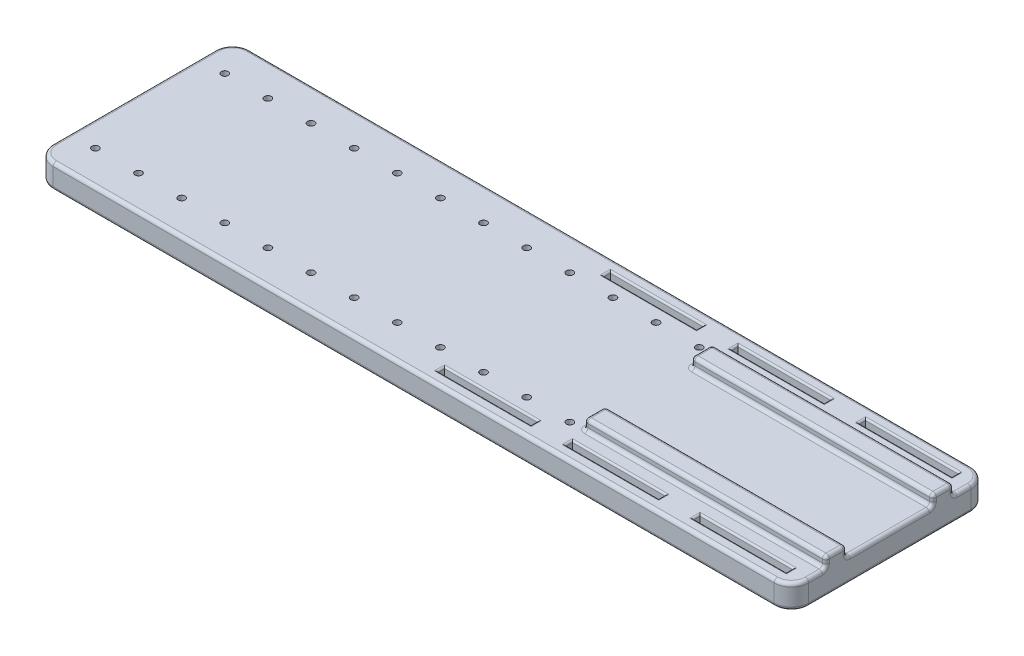
SolidWorks part; units mm, degrees
ref_plane "Front" through (0, 0, 0) normal (0, 0, 1) x (1, 0, 0)
ref_plane "Top" through (0, 0, 0) normal (0, 1, 0) x (1, 0, 0)
ref_plane "Right" through (0, 0, 0) normal (1, 0, 0) x (0, 0, -1)
sketch "Sketch6" plane through (0, 0, 0) normal (0, 0, 1) x (1, 0, 0)
  line L1 (-109.5, 3.5) -> (109.5, 3.5)
  line L2 (-109.5, 3.5) -> (-109.5, -3.5)
  line L3 (-109.5, -3.5) -> (109.5, -3.5)
  line L4 (109.5, 3.5) -> (109.5, -3.5)
  line L5 (-109.5, 3.5) -> (109.5, -3.5) construction
  line L6 (-109.5, -3.5) -> (109.5, 3.5) construction
  point P0 (0, 0)
  dimension "D1" = 219
  dimension "D2" = 7
extrude "Boss-Extrude2" add sketch "Sketch6" along normal mid plane 57
sketch "Sketch2" plane through (0, 3.5, 24.5) normal (0, -1, 0) x (1, 0, 0)
  line L0 (-109.5, -0.5) -> (109.5, -0.5) construction
  line L1 (54, -48.5) -> (54, -0.5) construction
  line L2 (91, -48.5) -> (91, -0.5) construction
  line L3 (17, -0.5) -> (17, -48.5) construction
  line L4 (3.5, 0.5) -> (30.5, 0.5)
  line L5 (3.5, 0.5) -> (3.5, -1.5)
  line L6 (3.5, -1.5) -> (30.5, -1.5)
  line L7 (30.5, 0.5) -> (30.5, -1.5)
  line L8 (3.5, 0.5) -> (30.5, -1.5) construction
  line L9 (3.5, -1.5) -> (30.5, 0.5) construction
  line L10 (40.5, 0.5) -> (67.5, 0.5)
  line L11 (40.5, 0.5) -> (40.5, -1.5)
  line L12 (40.5, -1.5) -> (67.5, -1.5)
  line L13 (67.5, 0.5) -> (67.5, -1.5)
  line L14 (40.5, 0.5) -> (67.5, -1.5) construction
  line L15 (40.5, -1.5) -> (67.5, 0.5) construction
  line L16 (77.5, 0.5) -> (104.5, 0.5)
  line L17 (77.5, 0.5) -> (77.5, -1.5)
  line L18 (77.5, -1.5) -> (104.5, -1.5)
  line L19 (104.5, 0.5) -> (104.5, -1.5)
  line L20 (77.5, 0.5) -> (104.5, -1.5) construction
  line L21 (77.5, -1.5) -> (104.5, 0.5) construction
  line L24 (-109.5, 4) -> (-109.5, -53) construction
  line L25 (109.5, 4) -> (109.5, -53) construction
  line L26 (109.5, 4) -> (-109.5, 4) construction
  line L27 (-109.5, -48.5) -> (109.5, -48.5) construction
  line L28 (109.5, -53) -> (-109.5, -53) construction
  line L30 (3.5, -49.5) -> (30.5, -49.5)
  line L31 (3.5, -49.5) -> (3.5, -47.5)
  line L32 (3.5, -47.5) -> (30.5, -47.5)
  line L33 (30.5, -49.5) -> (30.5, -47.5)
  line L34 (3.5, -49.5) -> (30.5, -47.5) construction
  line L35 (3.5, -47.5) -> (30.5, -49.5) construction
  line L36 (40.5, -49.5) -> (67.5, -49.5)
  line L37 (40.5, -49.5) -> (40.5, -47.5)
  line L38 (40.5, -47.5) -> (67.5, -47.5)
  line L39 (67.5, -49.5) -> (67.5, -47.5)
  line L40 (40.5, -49.5) -> (67.5, -47.5) construction
  line L41 (40.5, -47.5) -> (67.5, -49.5) construction
  line L42 (77.5, -49.5) -> (104.5, -49.5)
  line L43 (77.5, -49.5) -> (77.5, -47.5)
  line L44 (77.5, -47.5) -> (104.5, -47.5)
  line L45 (104.5, -49.5) -> (104.5, -47.5)
  line L46 (77.5, -49.5) -> (104.5, -47.5) construction
  line L47 (77.5, -47.5) -> (104.5, -49.5) construction
  point P5 (17, -48.5)
  point P6 (17, -0.5)
  point P11 (54, -0.5)
  point P16 (91, -0.5)
  point P32 (54, -48.5)
  point P37 (91, -48.5)
  dimension "D1" = 2
  dimension "D2" = 27
  dimension "D3" = 4.5
  dimension "D4" = 10
  dimension "D5" = 10
  dimension "D6" = 5
  dimension "D7" = 4.5
extrude "Cut-Extrude1" cut sketch "Sketch2" along normal up to surface (7 mm away) up to face at (0, -3.5, 0)
sketch "Sketch3" plane through (0, 3.5, 0) normal (0, 1, 0) x (1, 0, 0)
  line L0 (-109.5, 0) -> (109.5, 0) construction
  line L2 (35.5, 18.75) -> (35.5, -18.75) construction
  line L7 (40.5, -24) -> (30.5, -24) construction
  line L8 (40.5, -25) -> (40.5, -23) construction
  line L9 (-109.5, -28.5) -> (-109.5, 28.5) construction
  line L10 (109.5, -28.5) -> (109.5, 28.5) construction
  line L11 (30.5, -23) -> (30.5, -25) construction
  circle A2 centre (35.5, 18.75) radius 1
  circle A3 centre (35.5, -18.75) radius 1
  point P1 (35.5, -24)
  point P18 (35.5, 0)
  dimension "D2" = 2
  dimension "D1" = 37.5
extrude "Cut-Extrude2" cut sketch "Sketch3" against normal through all
sketch "Sketch4" plane through (0, -3.5, 0) normal (0, -1, 0) x (1, 0, 0)
  circle A0 centre (35.5, -18.75) radius 2
  circle A1 centre (35.5, 18.75) radius 2
  dimension "D1" = 4
extrude "Cut-Extrude3" cut sketch "Sketch4" against normal blind 1.75
fillet "Fillet3" radius 0.5 2 edges at (35.5, -3.5, -20.75) (35.5, -3.5, 16.75)
pattern_linear "LPattern1" count 12 spacing 12.5 along (-1, 0, 0) of "Fillet3", "Cut-Extrude2", "Cut-Extrude3"
fillet "Fillet2" radius 0.5 48 edges at (40.5, 3.5, 24) (54, 3.5, 25) (67.5, 3.5, 24) (54, 3.5, 23) (104.5, -3.5, 24) (91, -3.5, 25) (77.5, -3.5, 24) (91, -3.5, 23) (67.5, -3.5, 24) (54, -3.5, 25) (40.5, -3.5, 24) (54, -3.5, 23) (67.5, -3.5, -24) (54, -3.5, -23) (40.5, -3.5, -24) (54, -3.5, -25) (104.5, -3.5, -24) (91, -3.5, -23) (77.5, -3.5, -24) (91, -3.5, -25) (40.5, 3.5, -24) (54, 3.5, -23) (67.5, 3.5, -24) (54, 3.5, -25) (77.5, 3.5, -24) (91, 3.5, -23) (104.5, 3.5, -24) (91, 3.5, -25) (77.5, 3.5, 24) (91, 3.5, 25) (104.5, 3.5, 24) (91, 3.5, 23) (3.5, 3.5, -24) (17, 3.5, -23) (30.5, 3.5, -24) (17, 3.5, -25) (3.5, 3.5, 24) (17, 3.5, 25) (30.5, 3.5, 24) (17, 3.5, 23) (30.5, -3.5, 24) (17, -3.5, 25) (3.5, -3.5, 24) (17, -3.5, 23) (30.5, -3.5, -24) (17, -3.5, -23) (3.5, -3.5, -24) (17, -3.5, -25)
sketch "Sketch7" plane through (0, 3.5, 0) normal (0, 1, 0) x (1, 0, 0)
  line L0 (109.5, -28.5) -> (109.5, 28.5) construction
  line L1 (109.5, -18.5) -> (39.5, -18.5)
  line L2 (109.5, -18.5) -> (109.5, -12.5)
  line L3 (109.5, -12.5) -> (39.5, -12.5)
  line L4 (39.5, -18.5) -> (39.5, -12.5)
  line L5 (109.5, -28.5) -> (-109.5, -28.5) construction
  line L6 (109.5, 18.5) -> (39.5, 18.5)
  line L7 (109.5, 18.5) -> (109.5, 12.5)
  line L8 (109.5, 12.5) -> (39.5, 12.5)
  line L9 (39.5, 18.5) -> (39.5, 12.5)
  line L10 (109.5, 28.5) -> (-109.5, 28.5) construction
  dimension "D1" = 10
  dimension "D2" = 10
  dimension "D3" = 70
  dimension "D4" = 6
extrude "Boss-Extrude3" add sketch "Sketch7" along normal blind 3
fillet "Fillet4" radius 5 4 edges at (-109.5, 0, -28.5) (-109.5, 0, 28.5) (109.5, 0, 28.5) (109.5, 0, -28.5)
fillet "Fillet5" radius 1 40 edges at (109.5, 3.5, -21) (108.0355, 3.5, -27.0355) (109.5, 3.5, 21) (108.0355, 3.5, 27.0355) (0, 3.5, 28.5) (-108.0355, 3.5, 27.0355) (-109.5, 3.5, 0) (-108.0355, 3.5, -27.0355) (-108.0355, -3.5, -27.0355) (-109.5, -3.5, 0) (-108.0355, -3.5, 27.0355) (0, -3.5, 28.5) (108.0355, -3.5, 27.0355) (109.5, -3.5, 0) (108.0355, -3.5, -27.0355) (0, 3.5, -28.5) (0, -3.5, -28.5) (74.5, 3.5, 12.5) (74.5, 6.5, 12.5) (74.5, 6.5, 18.5) (74.5, 3.5, 18.5) (39.5, 5, 12.5) (39.5, 6.5, 15.5) (39.5, 5, 18.5) (39.5, 3.5, 15.5) (39.5, 3.5, -15.5) (39.5, 5, -12.5) (74.5, 3.5, -12.5) (39.5, 5, -18.5) (74.5, 3.5, -18.5) (109.5, 5, 18.5) (109.5, 6.5, 15.5) (109.5, 5, 12.5) (109.5, 3.5, 0) (109.5, 5, -12.5) (109.5, 5, -18.5) (74.5, 6.5, -12.5) (39.5, 6.5, -15.5) (74.5, 6.5, -18.5) (109.5, 6.5, -15.5)
sketch "Sketch5" plane through (0, -3.5, 0) normal (0, -1, 0) x (1, 0, 0)
  line L0 (109.5, -2.5) -> (0, -2.5) construction
  line L3 (0, 0) -> (109.5, 0) construction
  line L4 (109.5, 28.5) -> (109.5, -28.5) construction
  text T0 "KM-MB41-12-B" font "Calibri" height 5
  dimension "D1" = 2.5
extrude "Part Number Cut" cut sketch "Sketch5" against normal blind 0.6
equation "\"Screw Hole Spacing\"= 12.5mm"
equation "\"D3@LPattern1\"=\"Screw Hole Spacing\""
equation "\"D1@Sketch3\"=\"Screw Hole Spacing\"*3"
equation "\"Screw Hole Qty\"= 12"
equation "\"D1@LPattern1\"=\"Screw Hole Qty\""
equation "\"D1@Sketch6\"=69+\"Screw Hole Spacing\"*\"Screw Hole Qty\""
